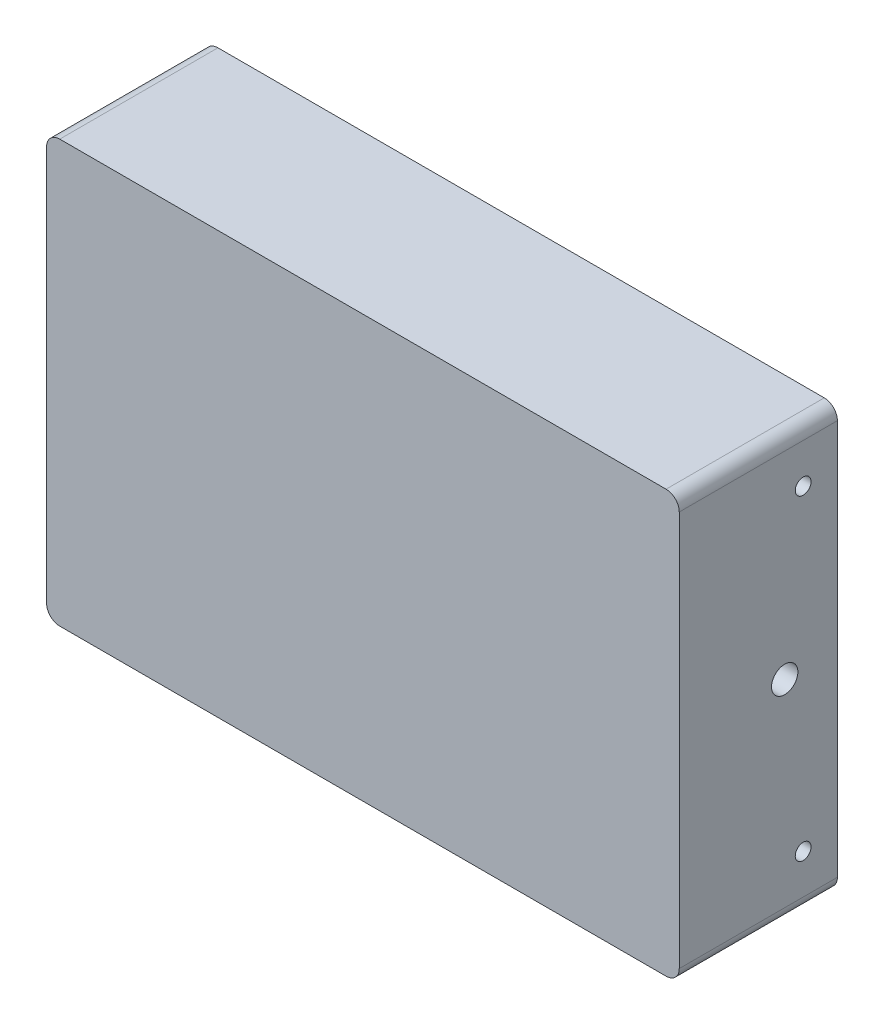
SolidWorks part; units mm, degrees
ref_plane "Front Plane" through (0, 0, 0) normal (0, 0, 1) x (1, 0, 0)
ref_plane "Top Plane" through (0, 0, 0) normal (0, 1, 0) x (1, 0, 0)
ref_plane "Right Plane" through (0, 0, 0) normal (1, 0, 0) x (0, 0, -1)
sketch "Sketch2" plane through (0, 0, 0) normal (0, 0, 1) x (1, 0, 0)
  line L1 (-37.5, 22.5) -> (37.5, 22.5)
  line L2 (-37.5, 22.5) -> (-37.5, -22.5)
  line L3 (-37.5, -22.5) -> (37.5, -22.5)
  line L4 (37.5, 22.5) -> (37.5, -22.5)
  line L5 (-37.5, 22.5) -> (37.5, -22.5) construction
  line L6 (-37.5, -22.5) -> (37.5, 22.5) construction
  line L7 (-37.5, 30) -> (37.5, 30)
  line L8 (-37.5, 30) -> (-37.5, -30)
  line L9 (-37.5, -30) -> (37.5, -30)
  line L10 (37.5, 30) -> (37.5, -30)
  line L11 (-37.5, 30) -> (37.5, -30) construction
  line L12 (-37.5, -30) -> (37.5, 30) construction
  line L18 (42.5, 22.5) -> (55, 22.5)
  line L19 (42.5, 22.5) -> (42.5, -22.5)
  line L20 (42.5, -22.5) -> (55, -22.5)
  line L21 (55, 22.5) -> (55, -22.5)
  line L22 (-55, 40) -> (55, 40)
  line L23 (-55, 40) -> (-55, -40)
  line L24 (-55, -40) -> (55, -40)
  line L25 (55, 40) -> (55, -40)
  line L26 (-55, 40) -> (55, -40) construction
  line L27 (-55, -40) -> (55, 40) construction
  circle A0 centre (-37.5, 30) radius 4
  circle A1 centre (37.5, 30) radius 4
  circle A2 centre (37.5, -30) radius 4
  circle A3 centre (-37.5, -30) radius 4
  point P0 (0, 0)
  point P5 (0, 0)
  point P23 (0, 0)
  dimension "D5" = 8
  dimension "D1" = 45
  dimension "D2" = 75
  dimension "D3" = 60
  dimension "D4" = 75
  dimension "D8" = 5
  dimension "D9" = 45
  dimension "D10" = 0
  dimension "D11" = 80
  dimension "D12" = 110
  dimension "D6" = 2
  dimension "D7" = 2
extrude "Boss-Extrude1" add sketch "Sketch2" along normal blind 20 contours L25 L22 L23 L24 L20 L19 L18 A3 L8 L2 A0 L7 A1 L10 L4 A2 L9 | A1 L7 A0 L8 L1 L10 | L4 L1 L2 L3 | A3 L9 A2 L10 L3 L8 region at (0, 26.154, 0) region at (0, 0, 0) region at (0, -26.154, 0) region at (41.1399, 0, 0)
sketch "Sketch3" plane through (0, 0, 20) normal (0, 0, 1) x (1, 0, 0)
  line L1 (-55, 40) -> (55, 40)
  line L2 (-55, 40) -> (-55, -40)
  line L3 (-55, -40) -> (55, -40)
  line L4 (55, 40) -> (55, -40)
  line L5 (-55, 40) -> (55, -40) construction
  line L6 (-55, -40) -> (55, 40) construction
  point P0 (0, 0)
  dimension "D1" = 110
  dimension "D2" = 80
extrude "Boss-Extrude2" add sketch "Sketch3" along normal blind 10
sketch "Sketch4" plane through (0, 0, 0) normal (0, 0, 1) x (1, 0, 0)
  line L1 (-45, 30) -> (45, 30)
  line L2 (-45, 30) -> (-45, -30)
  line L3 (-45, -30) -> (45, -30)
  line L4 (45, 30) -> (45, -30)
  line L5 (-45, 30) -> (45, -30) construction
  line L6 (-45, -30) -> (45, 30) construction
  line L7 (-46.25, 32.8) -> (-43.75, 32.8)
  line L8 (-46.25, 32.8) -> (-46.25, 27.2)
  line L9 (-46.25, 27.2) -> (-43.75, 27.2)
  line L10 (-43.75, 32.8) -> (-43.75, 27.2)
  line L11 (-46.25, 32.8) -> (-43.75, 27.2) construction
  line L12 (-46.25, 27.2) -> (-43.75, 32.8) construction
  line L20 (-46.25, -27.2) -> (-46.25, -32.8)
  line L21 (-46.25, -27.2) -> (-43.75, -27.2)
  line L22 (-43.75, -27.2) -> (-43.75, -32.8)
  line L23 (-46.25, -32.8) -> (-43.75, -32.8)
  line L32 (43.75, 32.8) -> (46.25, 32.8)
  line L33 (43.75, 32.8) -> (43.75, 27.2)
  line L34 (46.25, 32.8) -> (46.25, 27.2)
  line L35 (43.75, 27.2) -> (46.25, 27.2)
  line L36 (43.75, -27.2) -> (46.25, -27.2)
  line L37 (43.75, -27.2) -> (43.75, -32.8)
  line L38 (46.25, -27.2) -> (46.25, -32.8)
  line L39 (43.75, -32.8) -> (46.25, -32.8)
  line L40 (54.75, 32.8) -> (54.75, 27.2) [skipped]
  line L41 (54.75, 32.8) -> (57.25, 32.8) [skipped]
  line L42 (57.25, 32.8) -> (57.25, 27.2) [skipped]
  line L43 (54.75, 27.2) -> (57.25, 27.2) [skipped]
  line L44 (54.75, -27.2) -> (54.75, -32.8) [skipped]
  line L45 (54.75, -27.2) -> (57.25, -27.2) [skipped]
  line L46 (57.25, -27.2) -> (57.25, -32.8) [skipped]
  line L47 (54.75, -32.8) -> (57.25, -32.8) [skipped]
  point P0 (0, 0)
  point P5 (-45, 30)
  dimension "D1" = 2
  dimension "D2" = 5.6
  dimension "105" = 90
  dimension "D3" = 2.5
  dimension "D4" = 2
  dimension "D5" = 2
extrude "Cut-Extrude1" cut sketch "Sketch4" along normal blind 10 contours L4 L35 L34 L32 L33 L1 | L33 L35 L4 L1 | L10 L7 L8 L9 L2 L1 | L10 L1 L2 L9 | L22 L21 L2 L3 | L20 L23 L22 L3 L2 L21 | L37 L39 L38 L36 L4 L3 | L36 L37 L3 L4 region at (-45.2083, 30.4667, 0) region at (-44.375, 28.6, 0) region at (45.2083, 30.4667, 0) region at (44.375, 28.6, 0) region at (-44.375, -28.6, 0) region at (-45.2083, -30.4667, 0) region at (45.2083, -30.4667, 0) region at (44.375, -28.6, 0)
sketch "Sketch5" plane through (55, 0, 0) normal (1, 0, 0) x (0, 0, -1)
  line L0 (0, 22.5) -> (0, -22.5) construction
  line L1 (-30, 40) -> (0, 40)
  line L2 (-30, 40) -> (-30, -40)
  line L3 (-30, -40) -> (0, -40)
  line L4 (0, 40) -> (0, -40)
  line L5 (-30, 40) -> (0, 40) construction
  dimension "D1" = 80
  dimension "D2" = 30
  dimension "D3" = 0
  dimension "D4" = 0
extrude "Boss-Extrude4" add sketch "Sketch5" along normal blind 10
sketch "Sketch8" plane through (65, 0, 0) normal (1, 0, 0) x (0, 0, -1)
  line L0 (0, -40) -> (0, 40) construction
  circle A0 centre (-6.5, 30) radius 1.5
  circle A1 centre (-6.5, -30) radius 1.5
  dimension "D1" = 3
  dimension "D2" = 3
  dimension "D3" = 60
  dimension "D4" = 30
  dimension "D5" = 6.5
extrude "Cut-Extrude2" cut sketch "Sketch8" against normal blind 120
sketch "Sketch9" plane through (42.5, 0, 0) normal (1, 0, 0) x (0, 0, -1)
  line L0 (-30, 40) -> (-30, -40) construction
  circle A0 centre (-10, 0) radius 2.5
  dimension "D1" = 5
  dimension "D2" = 20
extrude "Cut-Extrude3" cut sketch "Sketch9" against normal blind 20 and the other way blind 40
sketch "Sketch10" plane through (0, 0, 0) normal (0, 0, -1) x (-1, 0, 0)
  line L0 (-42.5, 22.5) -> (-42.5, -22.5) construction
  line L1 (-37.5, 4) -> (-33.8, 4)
  line L2 (-37.5, 4) -> (-37.5, -4)
  line L3 (-37.5, -4) -> (-33.8, -4)
  line L4 (-33.8, 4) -> (-33.8, -4)
  line L5 (-61.2, 4) -> (-57.5, 4)
  line L6 (-61.2, 4) -> (-61.2, -4)
  line L7 (-61.2, -4) -> (-57.5, -4)
  line L8 (-57.5, 4) -> (-57.5, -4)
  line L9 (-55, -22.5) -> (-55, 22.5) construction
  point P14 (-57.5, 0)
  point P15 (-37.5, 0)
  dimension "D1" = 8
  dimension "D2" = 3.7
  dimension "D3" = 5
  dimension "D4" = 8
  dimension "D5" = 3.7
  dimension "D6" = 2.5
extrude "Cut-Extrude4" cut sketch "Sketch10" against normal blind 15
fillet "Fillet1" radius 2.5 4 edges at (65, 40, 15) (65, -40, 15) (-55, -40, 15) (-55, 40, 15)
